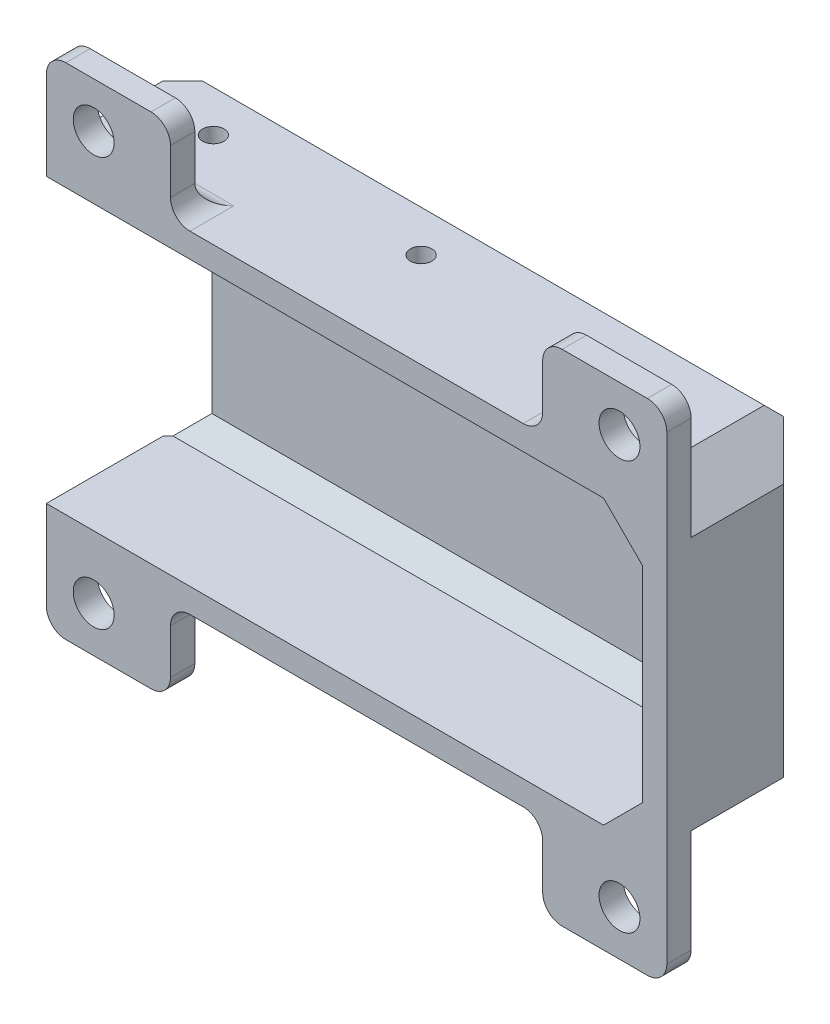
SolidWorks part; units mm, degrees
ref_plane "前视基准面" through (0, 0, 0) normal (0, 0, 1) x (1, 0, 0)
ref_plane "上视基准面" through (0, 0, 0) normal (0, 1, 0) x (1, 0, 0)
ref_plane "右视基准面" through (0, 0, 0) normal (1, 0, 0) x (0, 0, -1)
sketch "草图1" plane through (0, 0, 0) normal (0, 0, 1) x (1, 0, 0)
  line L1 (47.2241, 30.3103) -> (-6.7759, 30.3103) construction
  line L2 (47.2241, 30.3103) -> (47.2241, -11.6897) construction
  line L3 (47.2241, -11.6897) -> (-6.7759, -11.6897) construction
  line L4 (-6.7759, 30.3103) -> (-6.7759, -11.6897) construction
  line L5 (47.2241, 30.3103) -> (-6.7759, -11.6897) construction
  line L6 (47.2241, -11.6897) -> (-6.7759, 30.3103) construction
  line L7 (-11.6379, 34.9655) -> (52.0862, 34.9655)
  line L8 (-11.6379, 34.9655) -> (-11.6379, -16.3448)
  line L9 (-11.6379, -16.3448) -> (52.0862, -16.3448)
  line L10 (52.0862, 34.9655) -> (52.0862, -16.3448)
  line L11 (-11.6379, 34.9655) -> (52.0862, -16.3448) construction
  line L12 (-11.6379, -16.3448) -> (52.0862, 34.9655) construction
  circle A0 centre (47.2241, 30.3103) radius 2.1
  circle A1 centre (-6.7759, 30.3103) radius 2.1
  circle A2 centre (-6.7759, -11.6897) radius 2.1
  circle A3 centre (47.2241, -11.6897) radius 2.1
  point P0 (20.2241, 9.3103)
  point P9 (20.2241, 9.3103)
  dimension "D1" = 42
  dimension "D2" = 54
extrude "凸台-拉伸1" add sketch "草图1" along normal blind 2.5
sketch "草图2" plane through (0, 0, 0) normal (0, 0, -1) x (-1, 0, 0)
  line L0 (-52.0862, 9.3103) -> (-48.5569, 9.3103) construction
  line L2 (-20.2241, 34.9655) -> (-20.2241, 32.4809) construction
  line L4 (11.6379, 34.9655) -> (11.6379, -16.3448) construction
  line L5 (-52.0862, 26.3557) -> (11.6379, 26.3557)
  line L6 (-52.0862, 26.3557) -> (-52.0862, -7.735)
  line L7 (-52.0862, -7.735) -> (11.6379, -7.735)
  line L8 (11.6379, 26.3557) -> (11.6379, -7.735)
  line L9 (-52.0862, 26.3557) -> (11.6379, -7.735) construction
  line L10 (-52.0862, -7.735) -> (11.6379, 26.3557) construction
  point P2 (-20.2241, 9.3103)
extrude "凸台-拉伸2" add sketch "草图2" along normal blind 13.5
sketch "草图3" plane through (52.0862, 0, 0) normal (1, 0, 0) x (0, 0, -1)
  line L0 (-2.5, 9.3103) -> (2.413, 9.3103) construction
  line L2 (-2.5, -16.3448) -> (-2.5, 34.9655) construction
  line L3 (-17, 23.8557) -> (12, 23.8557)
  line L4 (-17, 23.8557) -> (-17, -5.235)
  line L5 (-17, -5.235) -> (12, -5.235)
  line L6 (12, 23.8557) -> (12, -5.235)
  line L7 (-17, 23.8557) -> (12, -5.235) construction
  line L8 (-17, -5.235) -> (12, 23.8557) construction
  line L9 (13.5, 26.3557) -> (13.5, -7.735) construction
  line L10 (13.5, 26.3557) -> (0, 26.3557) construction
  point P1 (-2.5, 9.3103)
  dimension "D1" = 1.5
  dimension "D2" = 2.5
extrude "切除-拉伸1" cut sketch "草图3" against normal through all both and the other way through all
chamfer "倒角1" distance 2 angle 45 4 edges at (20.2241, 26.3557, -13.5) (20.2241, -7.735, -13.5) (20.2241, -5.235, -12) (20.2241, 23.8557, -12)
sketch "草图4" plane through (0, 0, 0) normal (0, 0, -1) x (-1, 0, 0)
  line L0 (-20.2241, 34.9655) -> (-20.2241, 29.0132) construction
  line L2 (-52.0862, 34.9655) -> (11.6379, 34.9655) construction
  line L3 (-39.3359, 43.5754) -> (-1.1123, 43.5754)
  line L4 (-39.3359, 43.5754) -> (-39.3359, 26.3557)
  line L5 (-39.3359, 26.3557) -> (-1.1123, 26.3557)
  line L6 (-1.1123, 43.5754) -> (-1.1123, 26.3557)
  line L7 (-39.3359, 43.5754) -> (-1.1123, 26.3557) construction
  line L8 (-39.3359, 26.3557) -> (-1.1123, 43.5754) construction
  line L9 (11.6379, 26.3557) -> (-52.0862, 26.3557) construction
  line L10 (-52.0862, -7.735) -> (11.6379, -7.735) construction
  line L11 (-39.3359, -24.401) -> (-1.1123, -24.401)
  line L12 (-39.3359, -24.401) -> (-39.3359, -7.735)
  line L13 (-39.3359, -7.735) -> (-1.1123, -7.735)
  line L14 (-1.1123, -24.401) -> (-1.1123, -7.735)
  line L15 (-39.3359, -24.401) -> (-1.1123, -7.735) construction
  line L16 (-39.3359, -7.735) -> (-1.1123, -24.401) construction
  point P1 (-20.2241, 34.9655)
  point P11 (-20.2241, -16.068)
extrude "切除-拉伸2" cut sketch "草图4" against normal through all both and the other way through all
fillet "圆角1" radius 2 12 edges at (39.3359, -7.735, 1.25) (1.1123, -7.735, 1.25) (1.1123, 26.3557, 1.25) (1.1123, 34.9655, 1.25) (-11.6379, 34.9655, 1.25) (-11.6379, -16.3448, 1.25) (1.1123, -16.3448, 1.25) (39.3359, -16.3448, 1.25) (52.0862, -16.3448, 1.25) (39.3359, 26.3557, 1.25) (39.3359, 34.9655, 1.25) (52.0862, 34.9655, 1.25)
sketch "草图5" plane through (0, 0, -12) normal (0, 0, 1) x (1, 0, 0)
  line L0 (52.0862, 9.3103) -> (49.5933, 9.3103) construction
  line L2 (-11.6379, 23.8557) -> (52.0862, 23.8557) construction
  line L3 (49.5862, 23.8557) -> (52.0862, 23.8557)
  line L4 (49.5862, 23.8557) -> (49.5862, -5.235)
  line L5 (49.5862, -5.235) -> (52.0862, -5.235)
  line L6 (52.0862, 23.8557) -> (52.0862, -5.235)
  dimension "D1" = 2.5
extrude "凸台-拉伸3" add sketch "草图5" along normal up to surface (14.5 mm away) up to face at (20.2241, -12.0712, 2.5)
chamfer "倒角2" distance 1 angle 45 1 edges at (49.5862, 9.3103, -12)
chamfer "倒角3" distance 4 angle 45 6 edges at (52.0862, 26.3557, -5.75) (52.0862, -7.735, -5.75) (49.5862, -5.235, -3.75) (49.5862, 23.8557, -3.75) (52.0862, 9.3103, -13.5) (-11.6379, 9.3103, -13.5)
sketch "草图6" plane through (0, 26.3557, 0) normal (0, 1, 0) x (1, 0, 0)
  line L0 (-11.6379, 7.25) -> (-9.702, 7.25) construction
  circle A0 centre (-4.2353, 7.25) radius 1.1
  circle A1 centre (17.1021, 7.25) radius 1.1
  circle A2 centre (39.6196, 7.25) radius 1.1
extrude "切除-拉伸3" cut sketch "草图6" against normal blind 15.5
fillet "圆角2" radius 2 4 edges at (42.7111, 26.3557, 0) (-4.2628, 26.3557, 0) (42.7111, -7.735, 0) (-4.2628, -7.735, 0)
